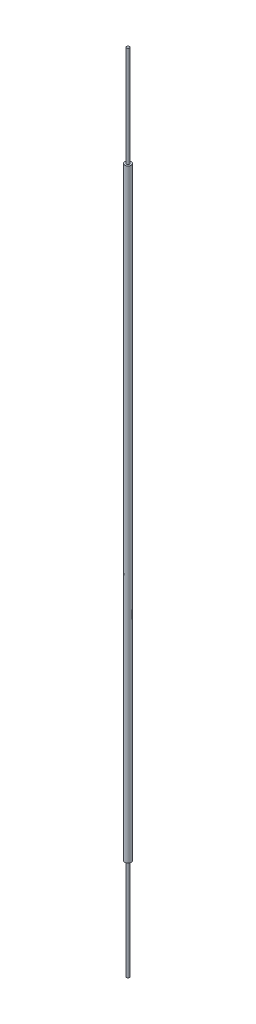
SolidWorks part; units mm, degrees
ref_plane "Front Plane" through (0, 0, 0) normal (0, 0, 1) x (1, 0, 0)
ref_plane "Top Plane" through (0, 0, 0) normal (0, 1, 0) x (1, 0, 0)
ref_plane "Right Plane" through (0, 0, 0) normal (1, 0, 0) x (0, 0, -1)
sketch "Sketch1" plane through (0, 0, 0) normal (0, 0, 1) x (1, 0, 0)
  line L0 (0, 0) -> (0, 33.8228) construction
  line L1 (0, 0) -> (0, 41.7864) construction
  line L2 (0, 0) -> (0, 5.5) construction
  line L3 (0, 5.5) -> (0, 24) construction
  line L4 (0, -3) -> (0, -6) construction
  spline S0 degree 3 poles (0, -6) (0, -5) (0, -4) (0, -3) (0, -2.0556) (0, -0.1667) (0, 2.6667) (0, 4.5556) (0, 5.5) (0, 11.6667) (0, 17.8333) (0, 24) knots 0 0 0 0 0.1 0.1 0.1 0.194444 0.288889 0.383333 0.383333 0.383333 1 1 1 1
  dimension "D1" = 0
  dimension "D2" = 5.5
  dimension "D3" = 18.5
  dimension "D4" = 3
  dimension "D5" = 3
  dimension "D6" = 0
ref_plane "Plane1" through (0, 24, 0) normal (0, 1, 0) x (1, 0, 0)
sketch "Sketch2" plane through (0, 24, 0) normal (0, 1, 0) x (1, 0, 0)
  circle A0 centre (0, 0) radius 0.1588
  circle A1 centre (0, 0) radius 0.0762
  dimension "D1" = 0.3175
  dimension "D2" = 0.1524
sweep "Sweep1" add profiles "Sketch2" path "Sketch1"
ref_plane "Plane2" through (0, 29, 0) normal (0, 1, 0) x (1, 0, 0)
sketch "Sketch3" plane through (0, 29, 0) normal (0, 1, 0) x (1, 0, 0)
  circle A0 centre (0, 0) radius 0.0698
  dimension "D1" = 0.1397
extrude "Boss-Extrude1" add sketch "Sketch3" against normal blind 40 separate body contours A0
